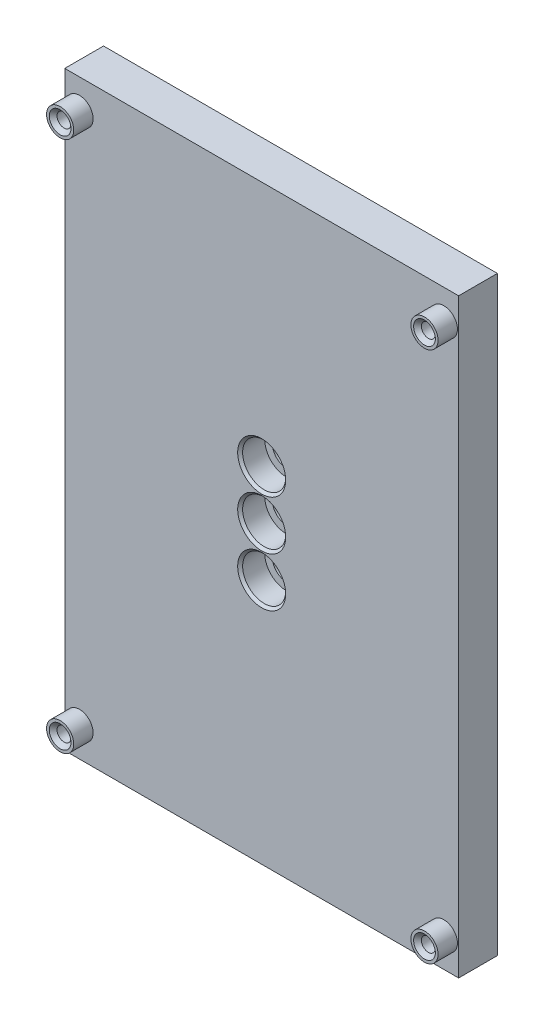
SolidWorks part; units mm, degrees
ref_plane "Front Plane" through (0, 0, 0) normal (0, 0, 1) x (1, 0, 0)
ref_plane "Top Plane" through (0, 0, 0) normal (0, 1, 0) x (1, 0, 0)
ref_plane "Right Plane" through (0, 0, 0) normal (1, 0, 0) x (0, 0, -1)
sketch "Sketch1" plane through (0, 0, 0) normal (0, 0, 1) x (1, 0, 0)
  line L1 (-50.8, 76.2) -> (50.8, 76.2)
  line L2 (-50.8, 76.2) -> (-50.8, -76.2)
  line L3 (-50.8, -76.2) -> (50.8, -76.2)
  line L4 (50.8, 76.2) -> (50.8, -76.2)
  line L5 (-50.8, 76.2) -> (50.8, -76.2) construction
  line L6 (-50.8, -76.2) -> (50.8, 76.2) construction
  point P0 (0, 0)
  dimension "D1" = 152.4
  dimension "D2" = 101.6
extrude "Boss-Extrude1" add sketch "Sketch1" along normal blind 10
hole_wizard "CBORE for 1/4 Socket Head Cap Screw1" positions "Sketch2" profile "Sketch4" counterbore size "1/4" standard "ANSI Inch" end condition through all
sketch "Sketch2" plane through (0, 0, 10) normal (0, 0, 1) x (1, 0, 0)
  point P0 (0, 12.7)
  point P2 (0, -12.7)
  point P10 (0, 0)
  point P13 (0, 0)
  dimension "D1" = 12.7
  dimension "D2" = 12.7
sketch "Sketch4" plane through (0, 12.7, 10) normal (1, 0, 0) x (0, -1, 0)
  line L0 (0, 0) -> (0, 10)
  line L1 (0, 10) -> (3.5712, 10)
  line L3 (3.5712, 10) -> (3.5712, 6.35)
  line L4 (5.5562, 6.35) -> (3.5712, 6.35)
  line L5 (5.5562, 6.35) -> (5.5562, 0.635)
  line L6 (5.5562, 0.635) -> (6.1913, 0)
  line L7 (6.1913, 0) -> (0, 0)
  line L8 (-5.5562, 0.635) -> (-6.1913, 0) construction
  line L11 (0, -6.35) -> (0, 107.95) construction
  dimension "Thru Hole Dia." = 7.1425
  dimension "Thru Hole Depth" = 10
  dimension "C'Bore Dia." = 11.1125
  dimension "C'Bore Depth" = 6.35
  dimension "Near C'Sink Dia." = 12.3825
  dimension "Near C'Sink Angle" = 90
sketch "Sketch5" plane through (0, 0, 10) normal (0, 0, 1) x (1, 0, 0)
  line L0 (-46.99, -68.58) -> (46.99, -68.58) construction
  line L1 (0, 0) -> (0, -68.58) construction
  line L2 (-46.99, 68.58) -> (46.99, 68.58) construction
  line L3 (0, 68.58) -> (0, 0) construction
  circle A0 centre (-46.99, -68.58) radius 3.5
  circle A1 centre (46.99, -68.58) radius 3.5
  circle A2 centre (-46.99, 68.58) radius 3.5
  circle A3 centre (46.99, 68.58) radius 3.5
  dimension "D1" = 7
  dimension "D2" = 93.98
  dimension "D3" = 137.16
extrude "Boss-Extrude2" add sketch "Sketch5" along normal blind 5
sketch "Sketch6" plane through (0, 0, 15) normal (0, 0, 1) x (1, 0, 0)
  circle A0 centre (46.99, 68.58) radius 1.8
  circle A1 centre (-46.99, 68.58) radius 1.8
  circle A2 centre (-46.99, -68.58) radius 1.8
  circle A3 centre (46.99, -68.58) radius 1.8
  dimension "D1" = 3.6
extrude "Cut-Extrude1" cut sketch "Sketch6" against normal through all
chamfer "Chamfer1" distance 1 angle 45 4 edges at (-45.19, -68.58, 15) (48.79, -68.58, 15) (-45.19, 68.58, 15) (48.79, 68.58, 15)
